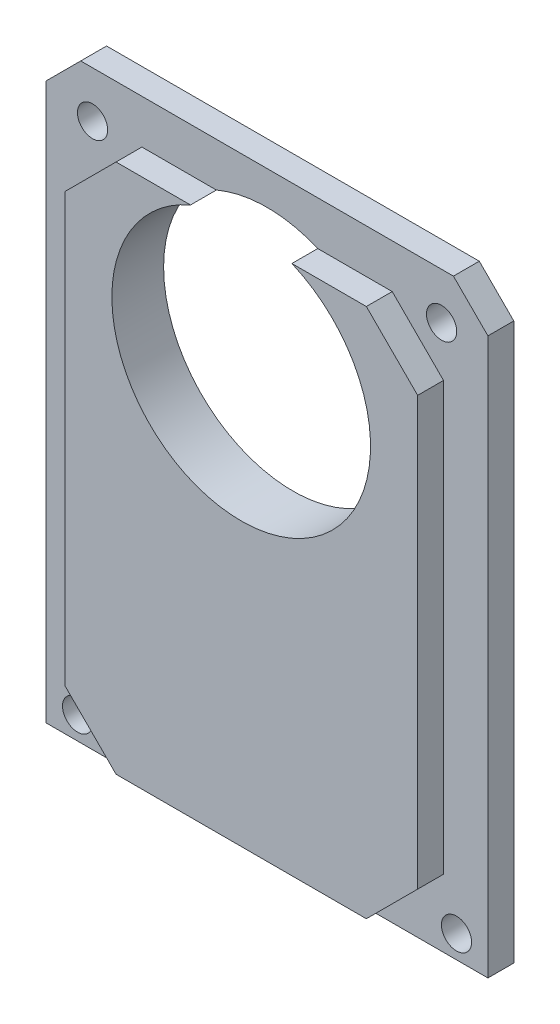
SolidWorks part; units mm, degrees
ref_plane "Front Plane" through (0, 0, 0) normal (0, 0, 1) x (1, 0, 0)
ref_plane "Top Plane" through (0, 0, 0) normal (0, 1, 0) x (1, 0, 0)
ref_plane "Right Plane" through (0, 0, 0) normal (1, 0, 0) x (0, 0, -1)
sketch "Sketch1" plane through (0, 0, 0) normal (0, 0, 1) x (1, 0, 0)
  line L1 (-25.615, -34.25) -> (25.615, -34.25)
  line L2 (-25.615, -34.25) -> (-25.615, 34.25)
  line L3 (-25.615, 34.25) -> (25.615, 34.25)
  line L4 (25.615, -34.25) -> (25.615, 34.25)
  line L5 (-25.615, -34.25) -> (25.615, 34.25) construction
  line L6 (-25.615, 34.25) -> (25.615, -34.25) construction
  point P0 (0, 0)
  dimension "D1" = 68.5
  dimension "D2" = 51.23
extrude "Boss-Extrude1" add sketch "Sketch1" along normal blind 3
chamfer "Chamfer1" distance 4 angle 45 2 edges at (25.615, 34.25, 1.5) (-25.615, 34.25, 1.5)
sketch "Sketch3" plane through (0, 0, 3) normal (0, 0, 1) x (1, 0, 0)
  line L5 (0, -34.25) -> (0, -1.6) construction
  line L6 (-25.615, -34.25) -> (25.615, -34.25) construction
  line L9 (-25.615, 30.25) -> (-25.615, -34.25) construction
  line L10 (-20.465, -32.35) -> (20.465, -32.35)
  line L11 (-20.465, -32.35) -> (-20.465, 29.15)
  line L12 (-20.465, 29.15) -> (20.465, 29.15)
  line L13 (20.465, -32.35) -> (20.465, 29.15)
  line L14 (-20.465, -32.35) -> (20.465, 29.15) construction
  line L15 (-20.465, 29.15) -> (20.465, -32.35) construction
  line L16 (25.615, -34.25) -> (25.615, 30.25) construction
  line L17 (21.615, 34.25) -> (-21.615, 34.25) construction
  point P0 (0, 0)
  dimension "D1" = 5.15
  dimension "D2" = 5.15
  dimension "D3" = 5.1
  dimension "D4" = 61.5
extrude "Boss-Extrude3" add sketch "Sketch3" along normal blind 3
chamfer "Chamfer2" distance 5.95 angle 45 4 edges at (20.465, -32.35, 4.5) (-20.465, -32.35, 4.5) (-20.465, 29.15, 4.5) (20.465, 29.15, 4.5)
sketch "Sketch4" plane through (0, 0, 3) normal (0, 0, 1) x (1, 0, 0)
  line L0 (-25.615, -34.25) -> (-21.9744, -31.605) construction
  line L1 (-25.615, -34.25) -> (25.615, -34.25) construction
  line L2 (25.615, -34.25) -> (21.9744, -31.605) construction
  line L3 (-23.615, 32.25) -> (-20.2421, 28.8771) construction
  line L4 (-21.615, 34.25) -> (-25.615, 30.25) construction
  line L5 (23.615, 32.25) -> (20.2421, 28.8771) construction
  line L6 (25.615, 30.25) -> (21.615, 34.25) construction
  circle A0 centre (-20.2421, 28.8771) radius 1.75
  circle A1 centre (20.2421, 28.8771) radius 1.75
  circle A2 centre (21.9744, -31.605) radius 1.75
  circle A3 centre (-21.9744, -31.605) radius 1.75
  dimension "D4" = 3.5
  dimension "D1" = 36
  dimension "D2" = 4.5
  dimension "D3" = 36
extrude "Cut-Extrude1" cut sketch "Sketch4" against normal through all
sketch "Sketch5" plane through (0, 0, 0) normal (0, 0, -1) x (-1, 0, 0)
  line L0 (0, -34.25) -> (0, 15.35) construction
  line L1 (25.615, -34.25) -> (-25.615, -34.25) construction
  circle A0 centre (0, 15.35) radius 15
  dimension "D1" = 30
  dimension "D2" = 49.6
extrude "Cut-Extrude2" cut sketch "Sketch5" against normal through all
ref_plane "Plane1" through (0, 0, 6) normal (0, 0, 1) x (1, 0, 0)
ref_plane "Plane2" through (-20.465, 0, 0) normal (-1, 0, 0) x (0, 0, 1)
ref_plane "Plane3" through (20.465, 0, 0) normal (1, 0, 0) x (0, 0, -1)
